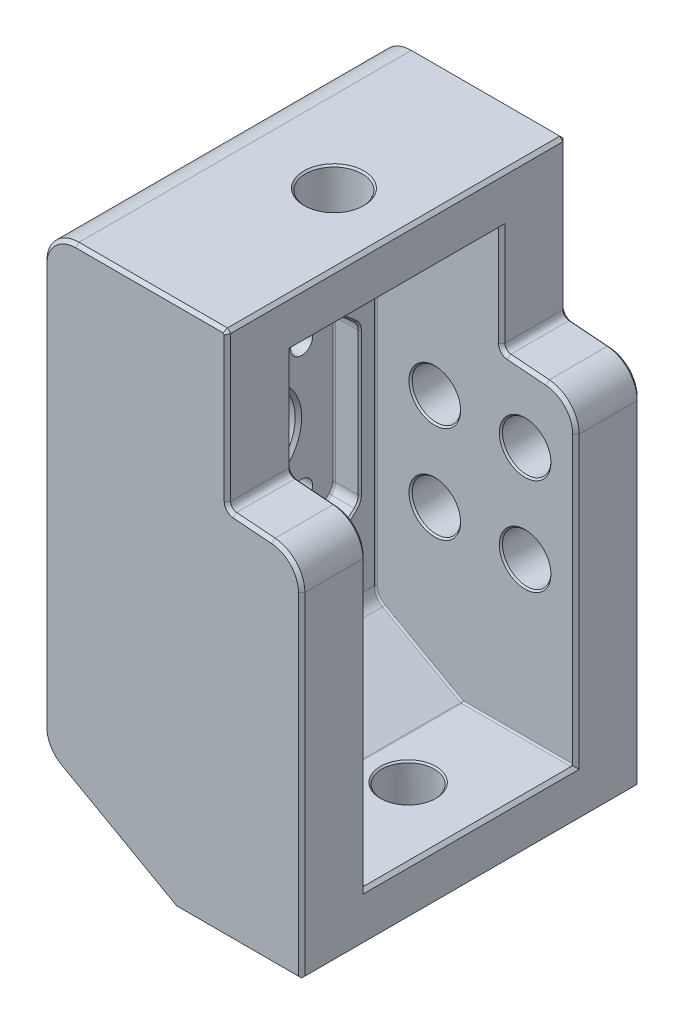
SolidWorks part; units mm, degrees
material "3.3549 (EN-AW 5182)"
ref_plane "Płaszczyzna przednia" through (0, 0, 0) normal (0, 0, 1) x (1, 0, 0)
ref_plane "Płaszczyzna górna" through (0, 0, 0) normal (0, 1, 0) x (1, 0, 0)
ref_plane "Płaszczyzna prawa" through (0, 0, 0) normal (1, 0, 0) x (0, 0, -1)
sketch "Szkic2" plane through (0, 0, 0) normal (0, 0, 1) x (1, 0, 0)
  line L0 (-74.8925, 20.1348) -> (-39, 0)
  line L14 (-23, 116.8791) -> (-23, 163)
  line L15 (-23, 163) -> (-80, 163)
  line L16 (-80, 163) -> (-80, 28.8563)
  line L18 (-39, 0) -> (0, 0)
  line L19 (0, 0) -> (0, 104)
  line L20 (-9.2351, 113.9707) -> (-21.153, 114.885)
  arc A0 (-80, 28.8563) -> (-74.8925, 20.1348) centre (-70, 28.8563) ccw
  arc A6 (-23, 116.8791) -> (-21.153, 114.885) centre (-21, 116.8791) ccw
  arc A8 (0, 104) -> (-9.2351, 113.9707) centre (-10, 104) ccw
  point P9 (-80, 23)
  dimension "D3" = 10
  dimension "D11" = 10
  dimension "D9" = 2
  dimension "D1" = 163
  dimension "D2" = 140
  dimension "D4" = 39
  dimension "D5" = 104
  dimension "D6" = 46.1209
  dimension "D7" = 57
  dimension "D8" = 80
  dimension "D10" = 0
extrude "Dodanie-wyciągnięcie1" add sketch "Szkic2" along normal blind 105
ref_plane "Płaszczyzna1" through (0, 0, 20) normal (0, 0, -1) x (-1, 0, 0)
sketch "Szkic3" plane through (0, 0, 20) normal (0, 0, -1) x (-1, 0, 0)
  line L0 (23, 163) -> (80, 163) construction
  line L1 (39, 0) -> (0, 0) construction
  line L2 (74.8925, 20.1348) -> (39, 0) construction
  line L5 (23, 116.8791) -> (23, 163) construction
  line L6 (9.2351, 113.9707) -> (21.153, 114.885) construction
  line L7 (0, 0) -> (0, 104) construction
  line L8 (80, 163) -> (80, 28.8563) construction
  line L21 (62, 33.0296) -> (62, 148)
  line L22 (62, 148) -> (23, 148)
  line L23 (23, 148) -> (23, 116.8791)
  line L24 (21.153, 114.885) -> (9.2351, 113.9707)
  line L25 (0, 104) -> (0, 15)
  line L26 (0, 15) -> (35.08, 15)
  line L27 (35.08, 15) -> (59.4463, 28.6689)
  arc A0 (21.153, 114.885) -> (23, 116.8791) centre (21, 116.8791) ccw construction
  arc A1 (9.2351, 113.9707) -> (0, 104) centre (10, 104) ccw
  arc A8 (59.4463, 28.6689) -> (62, 33.0296) centre (57, 33.0296) ccw
  arc A9 (21.153, 114.885) -> (23, 116.8791) centre (21, 116.8791) ccw
  dimension "D3" = 10
  dimension "D6" = 5
  dimension "D1" = 15
  dimension "D2" = 15
  dimension "D4" = 18
  dimension "D5" = 15
extrude "Wytnij-wyciągnięcie1" cut sketch "Szkic3" against normal blind 65
sketch "Szkic4" plane through (-80, 0, 0) normal (-1, 0, 0) x (0, 0, 1)
  line L0 (105, 163) -> (0, 163) construction
  line L1 (105, 163) -> (105, 28.8563) construction
  circle A0 centre (50, 81.5) radius 17.5
  dimension "D1" = 35
  dimension "D2" = 55
  dimension "81.5" = 81.5
extrude "Dodanie-wyciągnięcie2" add sketch "Szkic4" along normal blind 19
sketch "Szkic5" plane through (-99, 0, 0) normal (-1, 0, 0) x (0, 0, 1)
  circle A0 centre (50, 81.5) radius 14
  circle A1 centre (50, 81.5) radius 17.5 construction
  dimension "D1" = 28
extrude "Wytnij-wyciągnięcie2" cut sketch "Szkic5" against normal up to next
sketch "Szkic6" plane through (-99, 0, -93) normal (1, 0, 0) x (0, 0, -1)
  line L89 (-129.3105, 93.5237) -> (-127.1892, 91.4024)
  line L90 (-144.2, 98.4485) -> (-141.2, 98.4485)
  line L91 (-144.2, 98.4485) -> (-144.2, 95.4485)
  line L93 (-141.2, 98.4485) -> (-141.2, 95.4485)
  line L94 (-127.1892, 91.4024) -> (-129.3105, 89.281)
  line L95 (-129.3105, 93.5237) -> (-131.4318, 91.4024)
  line L96 (-122.2644, 79.5129) -> (-122.2644, 76.5129)
  line L97 (-122.2644, 76.5129) -> (-125.2644, 76.5129)
  line L98 (-122.2644, 79.5129) -> (-125.2644, 79.5129)
  line L99 (-127.1892, 64.6234) -> (-129.3105, 62.5021)
  line L100 (-129.3105, 62.5021) -> (-131.4318, 64.6234)
  line L101 (-127.1892, 64.6234) -> (-129.3105, 66.7447)
  line L102 (-141.2, 57.5773) -> (-144.2, 57.5773)
  line L103 (-144.2, 57.5773) -> (-144.2, 60.5773)
  line L104 (-141.2, 57.5773) -> (-141.2, 60.5773)
  line L105 (-156.0895, 62.5021) -> (-158.2108, 64.6234)
  line L106 (-158.2108, 64.6234) -> (-156.0895, 66.7447)
  line L107 (-156.0895, 62.5021) -> (-153.9682, 64.6234)
  line L108 (-163.1356, 76.5129) -> (-163.1356, 79.5129)
  line L109 (-163.1356, 79.5129) -> (-160.1356, 79.5129)
  line L110 (-163.1356, 76.5129) -> (-160.1356, 76.5129)
  line L111 (-158.2108, 91.4024) -> (-156.0895, 93.5237)
  line L112 (-156.0895, 93.5237) -> (-153.9682, 91.4024)
  line L113 (-158.2108, 91.4024) -> (-156.0895, 89.281)
  line L114 (-142.7, 78.0129) -> (-141.2, 95.4485) construction
  arc A27 (-131.4318, 91.4024) -> (-129.3105, 89.281) centre (-142.7, 78.0129) cw
  circle A36 centre (-143, 81.5) radius 14 construction
  arc A38 (-144.2, 95.4485) -> (-141.2, 95.4485) centre (-142.7, 78.0129) cw
  arc A39 (-125.2644, 79.5129) -> (-125.2644, 76.5129) centre (-142.7, 78.0129) cw
  arc A40 (-129.3105, 66.7447) -> (-131.4318, 64.6234) centre (-142.7, 78.0129) cw
  arc A41 (-141.2, 60.5773) -> (-144.2, 60.5773) centre (-142.7, 78.0129) cw
  arc A42 (-153.9682, 64.6234) -> (-156.0895, 66.7447) centre (-142.7, 78.0129) cw
  arc A43 (-160.1356, 76.5129) -> (-160.1356, 79.5129) centre (-142.7, 78.0129) cw
  arc A44 (-156.0895, 89.281) -> (-153.9682, 91.4024) centre (-142.7, 78.0129) cw
  dimension "D1" = 3
  dimension "D2" = 3
  dimension "D3" = 17.5
sketch "Szkic7" plane through (-62, 0, 0) normal (1, 0, 0) x (0, 0, -1)
  line L0 (0, 163) -> (0, 28.8563) construction
  line L1 (-71, 50) -> (-29, 50)
  line L2 (-76, 55) -> (-76, 120)
  line L3 (-71, 125) -> (-29, 125)
  line L4 (-24, 55) -> (-24, 120)
  line L5 (-76, 50) -> (-24, 125) construction
  line L6 (-76, 125) -> (-24, 50) construction
  arc A0 (-71, 50) -> (-76, 55) centre (-71, 55) cw
  arc A1 (-29, 50) -> (-24, 55) centre (-29, 55) ccw
  arc A2 (-29, 125) -> (-24, 120) centre (-29, 120) cw
  arc A3 (-76, 120) -> (-71, 125) centre (-71, 120) cw
  point P0 (-50, 87.5)
  dimension "D1" = 5
  dimension "D2" = 75
  dimension "D3" = 52
  dimension "D4" = 50
hole_wizard "Pogłębienie walcowe pod M8 Wkręt z łbem walcowym z gniazdem sześciokątnym1" positions "Szkic11" profile "Szkic12" counterbore size "M8" standard "ISO"
sketch "Szkic11" plane through (0, 0, 20) normal (0, 0, 1) x (1, 0, 0)
  line L0 (-23, 163) -> (-80, 163) construction
  point P0 (-43.7419, 93)
  point P2 (-15.7419, 93)
  point P4 (-43.7419, 63)
  point P6 (-15.7419, 63)
  dimension "D1" = 70
  dimension "D2" = 28
  dimension "D3" = 30
sketch "Szkic12" plane through (-43.7419, 93, 20) normal (1, 0, 0) x (0, -1, 0)
  line L0 (0, 0) -> (0, 50.2039)
  line L1 (0, 50.2039) -> (4.5, 47.5)
  line L2 (4.5, 47.5) -> (4.5, 8.6)
  line L3 (4.5, 8.6) -> (7.5, 8.6)
  line L4 (7.5, 8.6) -> (7.5, 0)
  line L5 (7.5, 0) -> (0, 0)
  line L10 (0, 50.2039) -> (-4.5, 47.5) construction
  line L11 (0, -6.35) -> (0, 107.95) construction
  dimension "Średnica otworu" = 9
  dimension "Głębokość otworu" = 47.5
  dimension "Średnica pogłębienia walcowego" = 15
  dimension "Głębokość pogłębienia walcowego" = 8.6
  dimension "Kąt wiertła" = 118
ref_plane "Płaszczyzna2" through (0, 0, 50) normal (0, 0, -1) x (-1, 0, 0)
sketch "Szkic13" plane through (0, 0, 50) normal (0, 0, -1) x (-1, 0, 0)
  line L0 (45, 167) -> (45, 148)
  line L1 (45, 167) -> (36, 167)
  line L2 (36, 167) -> (36.9, 148)
  line L3 (36.9, 148) -> (45, 148)
  line L4 (23, 116.8791) -> (23, 163) construction
  line L5 (23, 163) -> (80, 163) construction
  point P6 (40.5, 167)
  dimension "D1" = 9
  dimension "D2" = 8.1
  dimension "D3" = 22
  dimension "D4" = 19
  dimension "D5" = 4
revolve "Wycięcie-obrót1" cut sketch "Szkic13" angle 360 about L0
sketch "Szkic14" plane through (0, 0, 50) normal (0, 0, -1) x (-1, 0, 0)
  line L0 (22, -4) -> (22, 15)
  line L1 (22, -4) -> (13, -4)
  line L2 (22, 15) -> (13.9, 15)
  line L3 (13.9, 15) -> (13, -4)
  line L5 (23, 116.8791) -> (23, 163) construction
  line L6 (39, 0) -> (0, 0) construction
  point P2 (17.5, -4)
  dimension "D1" = 9
  dimension "D2" = 8.1
  dimension "D3" = 19
  dimension "D4" = 1
  dimension "D5" = 4
revolve "Wycięcie-obrót2" cut sketch "Szkic14" angle 360 about L0
ref_axis "Oś1" through (-45, 202.955, 50) along (0, -1, 0)
ref_axis "Oś2" through (-22, 0, 50) along (0, 1, 0)
fillet "Zaokrąglenie3" radius 10 1 edges at (-80, 163, 52.5)
chamfer "Sfazowanie3" distance 1 angle 45 12 edges at (-78.6292, 23.8028, 0) (-56.9463, 10.0674, 0) (-19.5, 0, 0) (0, 52, 0) (-2.6635, 110.7953, 0) (-15.194, 114.4278, 0) (-22.4673, 115.5201, 0) (-23, 139.9396, 0) (-46.5, 163, 0) (-77.0711, 160.0711, 0) (-80, 90.9281, 0) (-23, 163, 52.5)
chamfer "Sfazowanie4" distance 1 angle 45 12 edges at (-23, 139.4396, 105) (-22.4673, 115.5201, 105) (-15.194, 114.4278, 105) (-2.6635, 110.7953, 105) (0, 52, 105) (-19.5, 0, 105) (-56.9463, 10.0674, 105) (-78.6292, 23.8028, 105) (-80, 90.9281, 105) (-77.0711, 160.0711, 105) (-47, 163, 105) (-23.5, 162.5, 105)
chamfer "Sfazowanie6" distance 1 angle 45 1 edges at (0, 0, 52.5)
fillet "Zaokrąglenie4" radius 3 1 edges at (-39, 0, 52.5)
chamfer "Sfazowanie8" distance 1 angle 45 12 edges at (-23, 148, 52.5) (-23, 132.4396, 20) (-22.4673, 115.5201, 20) (-15.194, 114.4278, 20) (-2.6635, 110.7953, 20) (0, 59.5, 20) (0, 15, 52.5) (0, 59.5, 85) (-2.6635, 110.7953, 85) (-15.194, 114.4278, 85) (-22.4673, 115.5201, 85) (-23, 132.4396, 85)
fillet "Zaokrąglenie5" radius 0.5 11 edges at (-47.2631, 21.8344, 20) (-61.3146, 30.5028, 20) (-47.2631, 21.8344, 85) (-61.3146, 30.5028, 85) (-62, 90.5148, 20) (-43, 148, 20) (-62, 90.5148, 85) (-62, 148, 52.5) (-43, 148, 85) (-18.04, 15, 20) (-18.04, 15, 85)
chamfer "Sfazowanie13" distance 0.5 angle 45 4 edges at (-45, 148, 58.1) (-13.9, 15, 50) (-22, 0, 58.8105) (-45, 163, 41.1895) first distance on face at (-45, 148, 58.1) first distance on face at (-13.9, 15, 50) first distance on face at (-45, 163, 41.1895)
chamfer "Sfazowanie14" distance 0.5 angle 45 8 edges at (-8.2419, 63, 20) (-36.2419, 63, 20) (-8.2419, 93, 20) (-36.2419, 93, 20) (-11.2419, 63, 0) (-39.2419, 63, 0) (-39.2419, 93, 0) (-11.2419, 93, 0)
sketch "Szkic16" plane through (0, 0, 11.4) normal (0, 0, 1) x (1, 0, 0)
  circle A1 centre (-43.7419, 93) radius 7.5
  circle A2 centre (-43.7419, 93) radius 7.5
  circle A4 centre (-15.7419, 63) radius 7.5 construction
  circle A5 centre (-15.7419, 63) radius 4.5 construction
  circle A6 centre (-15.7419, 93) radius 4.5 construction
  circle A7 centre (-15.7419, 93) radius 7.5 construction
  circle A8 centre (-43.7419, 63) radius 7.5 construction
  circle A9 centre (-43.7419, 63) radius 4.5 construction
  circle A10 centre (-43.7419, 93) radius 4.5 construction
  circle A11 centre (-15.7419, 63) radius 7.5
  circle A12 centre (-15.7419, 63) radius 4.5
  circle A13 centre (-15.7419, 93) radius 4.5
  circle A14 centre (-15.7419, 93) radius 7.5
  circle A15 centre (-43.7419, 63) radius 7.5
  circle A16 centre (-43.7419, 63) radius 4.5
  circle A17 centre (-43.7419, 93) radius 4.5
  dimension "D1" = 0
extrude "Wytnij-wyciągnięcie8" cut sketch "Szkic16" against normal blind 2.5
sketch "Szkic17" plane through (-62, 0, 0) normal (1, 0, 0) x (0, 0, -1)
  line L0 (-75, 105.275) -> (-75, 57.725)
  line L1 (-25, 105.275) -> (-25, 57.725)
  circle A0 centre (-50, 81.5) radius 14 construction
  arc A12 (-75, 57.725) -> (-25, 57.725) centre (-50, 81.5) ccw
  arc A13 (-25, 105.275) -> (-75, 105.275) centre (-50, 81.5) ccw
  point P2 (-75, 81.5)
  dimension "D1" = 50
  dimension "D2" = 69
extrude "Wytnij-wyciągnięcie10" cut sketch "Szkic17" against normal blind 8
fillet "Zaokrąglenie8" radius 4 4 edges at (-66, 57.725, 75) (-66, 57.725, 25) (-66, 105.275, 25) (-66, 105.275, 75)
hole_wizard "Otwór gwintowany M81" positions "Szkic22" profile "Szkic23" tap size "M8" standard "ISO"
sketch "Szkic22" plane through (-70, 0, 0) normal (1, 0, 0) x (0, 0, -1)
  line L0 (-50, 95.5) -> (-50, 67.5) construction
  line L2 (-64, 81.5) -> (-36, 81.5) construction
  circle A0 centre (-50, 81.5) radius 14 construction
  point P0 (-65, 101.5)
  point P2 (-50, 107.5)
  point P4 (-35, 101.5)
  point P6 (-65, 61.5)
  point P8 (-50, 55.5)
  point P10 (-35, 61.5)
  dimension "D1" = 15
  dimension "D2" = 15
  dimension "D3" = 6
  dimension "D4" = 6
  dimension "D5" = 20
  dimension "D6" = 20
sketch "Szkic23" plane through (-70, 101.5, 65) normal (0, 1, 0) x (0, 0, -1)
  line L0 (0, 0) -> (0, 24.2929)
  line L1 (0, 24.2929) -> (3.4, 22.25)
  line L2 (3.4, 22.25) -> (3.4, 0)
  line L5 (3.4, 0) -> (0, 0)
  line L10 (0, 24.2929) -> (-3.4, 22.25) construction
  line L11 (0, -6.35) -> (0, 107.95) construction
  dimension "Średnica wiertła gwintu" = 6.8
  dimension "Głębokość otworu gwintowanego" = 22.25
  dimension "Kąt wiertła" = 118
cosmetic thread "Gwint otworu1" parameters "D1"=16, "D2"=8
cosmetic thread "Gwint otworu2" parameters "D1"=16, "D2"=8
cosmetic thread "Gwint otworu3" parameters "D1"=16, "D2"=8
cosmetic thread "Gwint otworu4" parameters "D1"=16, "D2"=8
cosmetic thread "Gwint otworu5" parameters "D1"=16, "D2"=8
cosmetic thread "Gwint otworu6" parameters "D1"=16, "D2"=8
chamfer "Sfazowanie15" distance 0.5 angle 45 8 edges at (-62, 57.8025, 74.6753) (-62, 47, 50) (-62, 57.8025, 25.3247) (-62, 81.5, 25) (-62, 105.1975, 25.3247) (-62, 116, 50) (-62, 105.1975, 74.6753) (-62, 81.5, 75)
fillet "Zaokrąglenie9" radius 0.5 8 edges at (-70, 105.1975, 74.6753) (-70, 116, 50) (-70, 105.1975, 25.3247) (-70, 81.5, 25) (-70, 57.8025, 25.3247) (-70, 47, 50) (-70, 57.8025, 74.6753) (-70, 81.5, 75)
fillet "Zaokrąglenie10" [suppressed] radius 1
sketch "Szkic24" plane through (-99, 0, 0) normal (-1, 0, 0) x (0, 0, 1)
  line L0 (50, 99) -> (50, 64) construction
  line L1 (45, 92) -> (55, 92)
  line L2 (45, 92) -> (45, 98.6)
  line L3 (45.4, 99) -> (54.6, 99)
  line L4 (55, 92) -> (55, 98.6)
  line L5 (45, 92) -> (55, 99) construction
  line L6 (45, 99) -> (55, 92) construction
  circle A0 centre (50, 81.5) radius 14 construction
  arc A1 (54.6, 99) -> (55, 98.6) centre (54.6, 98.6) cw
  arc A2 (45, 98.6) -> (45.4, 99) centre (45.4, 98.6) cw
  circle A6 centre (50, 81.5) radius 17.5 construction
  point P0 (50, 95.5)
  dimension "D3" = 0.4
  dimension "D1" = 3.5
  dimension "D2" = 10
fillet "Zaokrąglenie11" radius 0.5 3 edges at (-35.0417, 15.1464, 84.8536) (-35.0417, 15.1464, 20.1464) (-35.08, 15, 52.5)
fillet "Zaokrąglenie12" radius 1 1 edges at (-80, 99, 50)
chamfer "Sfazowanie16" distance 1 angle 45 3 edges at (-70, 95.5, 50) (-99, 67.5, 50) (-99, 64, 50)
